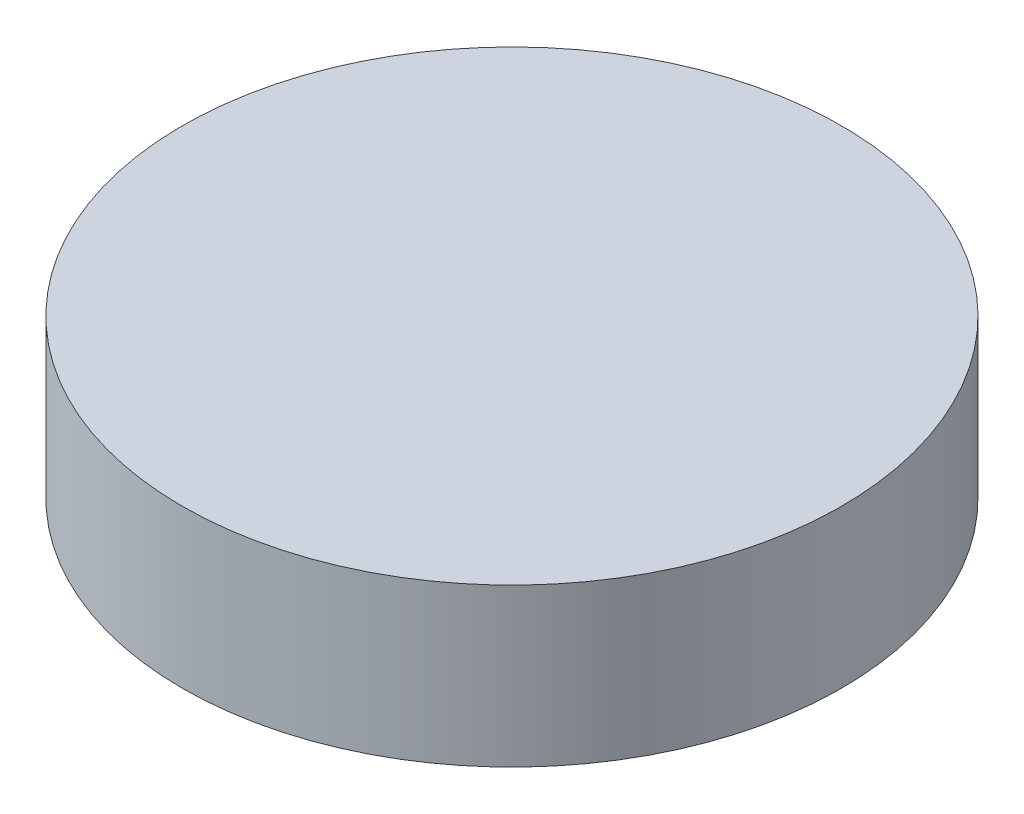
SolidWorks part; units mm, degrees
ref_plane "Front Plane" through (0, 0, 0) normal (0, 0, 1) x (1, 0, 0)
ref_plane "Top Plane" through (0, 0, 0) normal (0, 1, 0) x (1, 0, 0)
ref_plane "Right Plane" through (0, 0, 0) normal (1, 0, 0) x (0, 0, -1)
sketch "Sketch1" plane through (0, 0, 0) normal (0, 1, 0) x (1, 0, 0)
  circle A0 centre (0, 0) radius 10.325
  dimension "D1" = 20.65
extrude "Boss-Extrude1" add sketch "Sketch1" along normal blind 4.938
